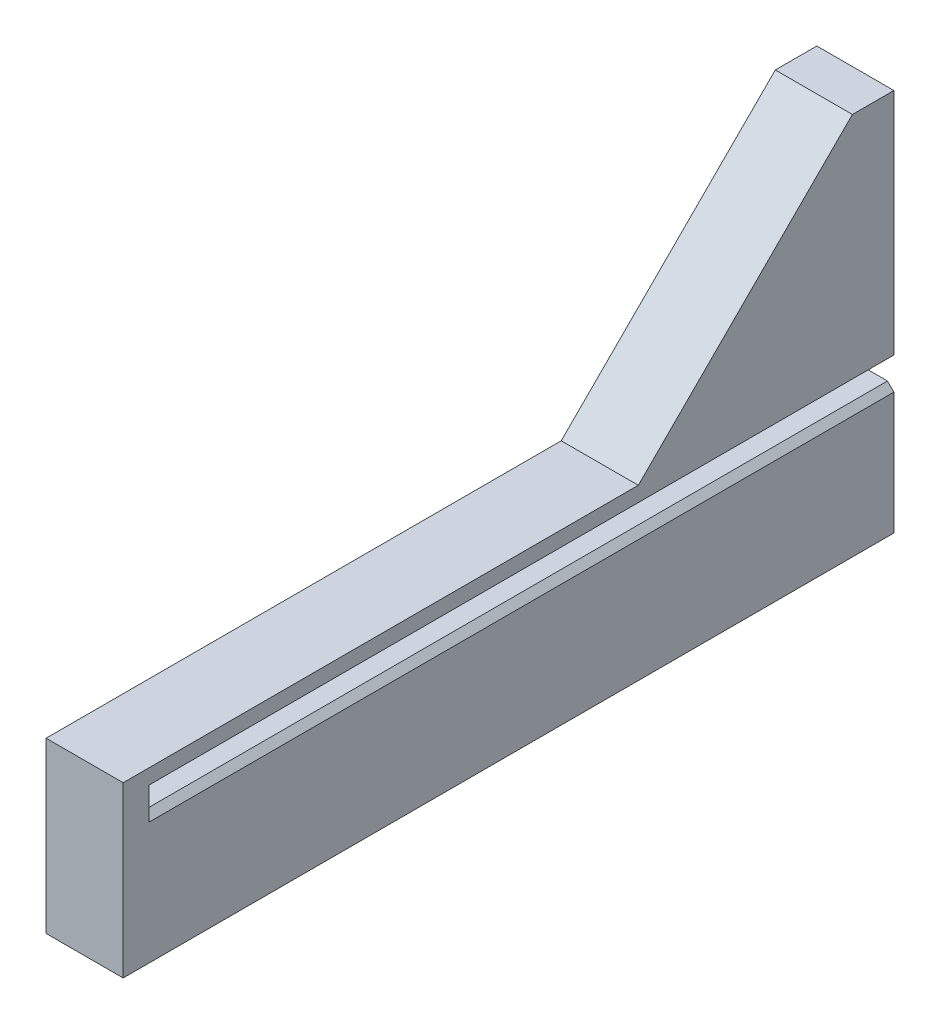
SolidWorks part; units mm, degrees
ref_plane "Спереди" through (0, 0, 0) normal (0, 0, 1) x (1, 0, 0)
ref_plane "Сверху" through (0, 0, 0) normal (0, 1, 0) x (1, 0, 0)
ref_plane "Справа" through (0, 0, 0) normal (1, 0, 0) x (0, 0, -1)
sketch "Эскиз1" plane through (0, 0, 0) normal (0, 0, 1) x (1, 0, 0)
  line L1 (-4.5, -7.5) -> (4.5, -7.5)
  line L2 (-4.5, -7.5) -> (-4.5, 7.5)
  line L3 (-4.5, 7.5) -> (4.5, 7.5)
  line L4 (4.5, -7.5) -> (4.5, 7.5)
  line L5 (-4.5, -7.5) -> (4.5, 7.5) construction
  line L6 (-4.5, 7.5) -> (4.5, -7.5) construction
  line L7 (-4.5, 7.5) -> (4.5, 7.5)
  line L8 (-4.5, 7.5) -> (-4.5, 12.25)
  line L9 (-4.5, 12.25) -> (4.5, 12.25)
  line L10 (4.5, 7.5) -> (4.5, 12.25)
  line L11 (4.5, 7.5) -> (-0.5, 7.5)
  line L12 (4.5, 7.5) -> (4.5, 9.75)
  line L13 (4.5, 9.75) -> (-0.5, 9.75)
  line L14 (-0.5, 7.5) -> (-0.5, 9.75)
  point P0 (0, 0)
  dimension "D1" = 9
  dimension "D2" = 15
  dimension "D3" = 2.25
  dimension "D4" = 2.5
  dimension "D5" = 4
extrude "Бобышка-Вытянуть1" add sketch "Эскиз1" along normal blind 90 contours L1 L4 L7 L3 L2 | L3 L14 L13 L10 L9 L8 region at (0, 0, 0) region at (-0.7143, 10.3214, 0)
sketch "Эскиз2" plane through (0, -7.5, 0) normal (0, -1, 0) x (1, 0, 0)
  line L0 (0, 90) -> (0, 67.5) construction
  line L1 (-4.5, 90) -> (4.5, 90) construction
  line L2 (0, 67.5) -> (0, 45) construction
  line L3 (0, 22.5) -> (0, 0) construction
  line L4 (-4.5, 0) -> (4.5, 0) construction
  line L5 (0, 45) -> (0, 22.5) construction
  circle A0 centre (0, 22.5) radius 2.1
  circle A1 centre (0, 67.5) radius 2.1
  circle A2 centre (0, 45) radius 2.1
  dimension "D1" = 4.2
extrude "Вырез-Вытянуть1" cut sketch "Эскиз2" against normal blind 6
sketch "Эскиз3" plane through (0, 0, 90) normal (0, 0, -1) x (-1, 0, 0)
  line L1 (-4.5, 9.75) -> (0.5, 9.75)
  line L2 (-4.5, 9.75) -> (-4.5, 7.5)
  line L3 (-4.5, 7.5) -> (0.5, 7.5)
  line L4 (0.5, 9.75) -> (0.5, 7.5)
extrude "Бобышка-Вытянуть2" add sketch "Эскиз3" along normal blind 3
chamfer "Фаска1" distance 0.75 angle 45 2 edges at (4.5, 7.5, 43.5) (4.5, 9.75, 43.5)
sketch "Эскиз5" plane through (-4.5, 0, 0) normal (-1, 0, 0) x (0, 0, 1)
  line L0 (0, 12.25) -> (0, 37.25)
  line L1 (0, 37.25) -> (4.8479, 37.25)
  line L2 (4.8479, 37.25) -> (29.8479, 12.25)
  line L3 (90, 12.25) -> (0, 12.25) construction
  line L4 (0, 12.25) -> (29.8479, 12.25)
  dimension "D1" = 45
  dimension "D2" = 25
extrude "Бобышка-Вытянуть3" add sketch "Эскиз5" against normal up to surface (9 mm away) contours L1 L2 L4 L0 up to face at (4.5, 5.5, 44.25)
sketch "Эскиз4" plane through (0, 0, 0) normal (0, 0, -1) x (-1, 0, 0)
  line L0 (-4.5, 37.25) -> (4.5, 37.25) construction
  line L1 (4.5, -7.5) -> (-4.5, -7.5) construction
  circle A0 centre (0, 2.5) radius 2.1
  circle A1 centre (0, 27.25) radius 2.1
  dimension "D1" = 4.2
  dimension "D2" = 10
  dimension "D3" = 10
extrude "Вырез-Вытянуть2" cut sketch "Эскиз4" against normal blind 6
mirror "Зеркальное отражение1" [suppressed] of bodies 104
delete or keep bodies "Тело-Удалить/Сохранить 1" [suppressed] type delete bodies bodies 104
